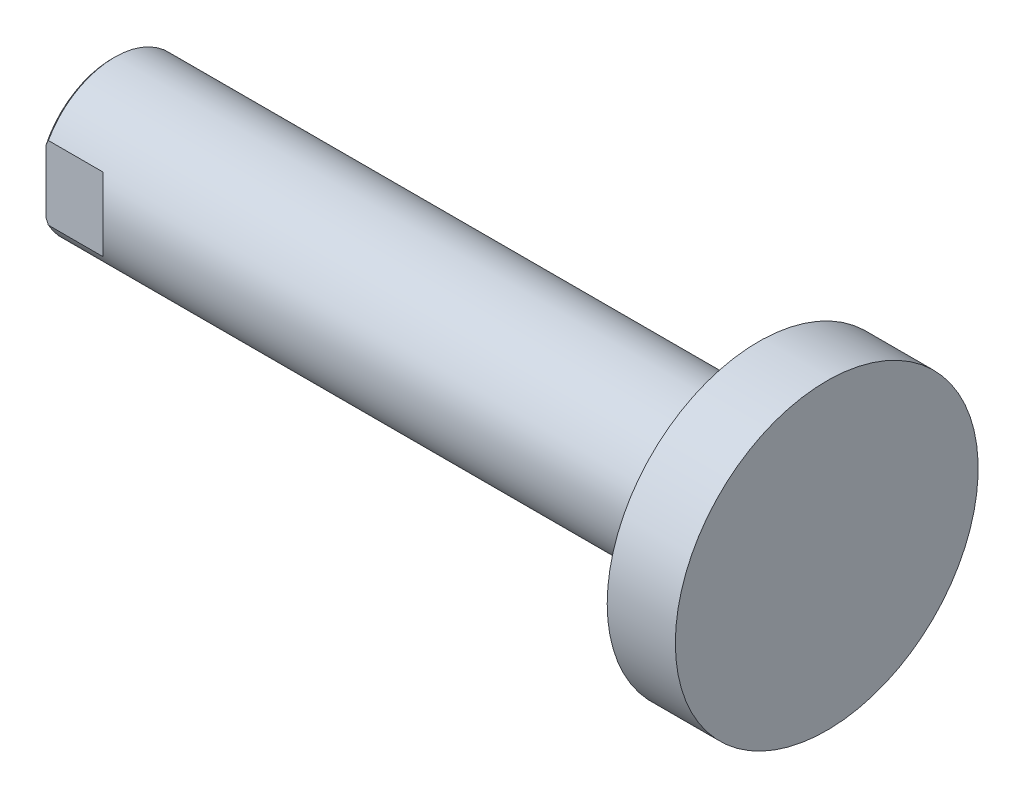
SolidWorks part; units mm, degrees
ref_plane "前视基准面" through (0, 0, 0) normal (0, 0, 1) x (1, 0, 0)
ref_plane "上视基准面" through (0, 0, 0) normal (0, 1, 0) x (1, 0, 0)
ref_plane "右视基准面" through (0, 0, 0) normal (1, 0, 0) x (0, 0, -1)
sketch "草图1" plane through (0, 0, 0) normal (0, 0, 1) x (1, 0, 0)
  line L0 (-7, 0) -> (-7, 7.75)
  line L1 (-7, 7.75) -> (-6.75, 8)
  line L2 (-6.75, 8) -> (0, 8)
  line L3 (0, 8) -> (0, 0)
  line L4 (0, 0) -> (-7, 0)
  line L5 (0, 0) -> (-7, 0) construction
revolve "旋转1" add sketch "草图1" angle 360 about L5 reverse direction yes
sketch "草图2" plane through (0, 0, 0) normal (0, 0, 1) x (1, 0, 0)
  line L0 (0, 0) -> (0, 8)
  line L1 (0, 8) -> (61.3, 8)
  line L2 (61.3, 8) -> (61.3, 16)
  line L3 (61.3, 16) -> (68.5, 16)
  line L4 (68.5, 16) -> (68.5, 0)
  line L5 (68.5, 0) -> (0, 0)
  line L6 (68.5, 0) -> (0, 0) construction
revolve "旋转2" add sketch "草图2" angle 360 about L6 reverse direction yes
sketch "草图3" plane through (0, 0, 0) normal (0, 1, 0) x (1, 0, 0)
  line L0 (-17, -12) -> (4, -12)
  line L1 (4, -12) -> (-1, -7)
  line L2 (-1, -7) -> (-7, -7)
  line L3 (-7, -7) -> (-7, 7)
  line L4 (-7, 7) -> (-1, 7)
  line L5 (-1, 7) -> (4, 12)
  line L6 (4, 12) -> (-17, 12)
  line L7 (-17, 12) -> (-17, -12)
extrude "切除-拉伸1" cut sketch "草图3" along normal blind 14 and the other way blind 14
hole_wizard "孔1" positions "草图5" profile "草图4" legacy
sketch "草图5" plane through (-7, 0, 0) normal (-1, 0, 0) x (0, 0, 1)
  point P0 (0, 0)
sketch "草图4" plane through (-7, 0, 0) normal (0, 1, 0) x (0, 0, 1)
  line L0 (0, 0) -> (0, 17.5188)
  line L1 (0, 17.5188) -> (3.3235, 15.6)
  line L2 (3.3235, 15.6) -> (3.3235, 0.6765)
  line L3 (3.3235, 0.6765) -> (4, 0)
  line L4 (4, 0) -> (0, 0)
  line L5 (0, -14.3089) -> (0, 102.4216) construction
  line L6 (0, 17.5188) -> (-3.3235, 15.6) construction
  line L7 (-3.3235, 0.6765) -> (-4, 0) construction
  dimension "直径" = 6.647
  dimension "深度" = 15.6
  dimension "锥坑直径" = 8
  dimension "锥坑角度" = 90
  dimension "导头角度" = 120
cosmetic thread "装饰螺纹线1" parameters "D1"=13, "D2"=8
ref_plane "基准面1" through (0, 0, 0) normal (1, 0, 0) x (0, 0, -1)
ref_plane "rod XY" through (0, 0, 0) normal (1, 0, 0) x (0, 0, -1)
ref_plane "rod XZ" through (0, 0, 0) normal (0, -1, 0) x (-1, 0, 0)
ref_plane "rod YZ" through (0, 0, 0) normal (0, 0, -1) x (-1, 0, 0)
ref_axis "rod X" through (0, 0, 80.9) along (0, 0, -1)
ref_axis "rod Y" through (0, -50, 0) along (0, 1, 0)
ref_axis "rod Z" through (80.9, 0, 0) along (-1, 0, 0)
sketch3d "rod"
  point P0 (0, 0, 0)
